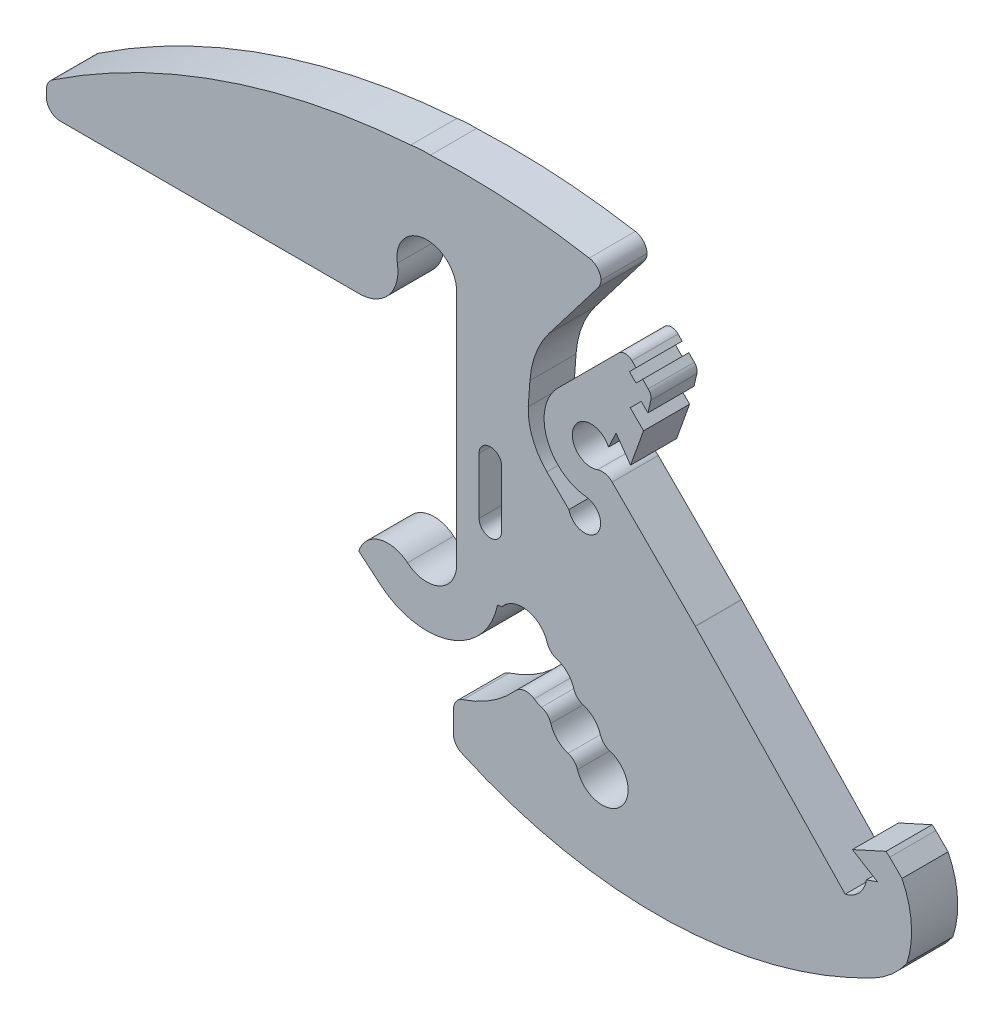
SolidWorks part; units mm, degrees
ref_plane "Front Plane" through (0, 0, 0) normal (0, 0, 1) x (1, 0, 0)
ref_plane "Top Plane" through (0, 0, 0) normal (0, 1, 0) x (1, 0, 0)
ref_plane "Right Plane" through (0, 0, 0) normal (1, 0, 0) x (0, 0, -1)
sketch "Main Geometry" plane through (0, 0, 0) normal (0, 0, 1) x (1, 0, 0)
  line L0 (0, -26.7735) -> (0, 29.7025) construction
  line L1 (-29.8398, 0) -> (33.7757, 0) construction
  line L2 (18, -21.6476) -> (18, 5) construction
  line L3 (18, 5) -> (48.2234, -25.2234) construction
  dimension "vertical offset" = 5
  dimension "horizontal offset" = 18
  dimension "device angle" = 45
sketch "Cart Clip Geometry" plane through (0, 0, 0) normal (0, 0, 1) x (1, 0, 0)
  line L0 (18, 9.2735) -> (18, -10.0482) construction
  line L1 (11.175, 4.575) -> (7.675, -8.575)
  line L2 (7.0852, 12.575) -> (-7.0852, 12.575) construction
  line L3 (-29.8398, 0) -> (33.7757, 0) construction
  line L4 (18, -21.6476) -> (18, 5) construction
  line L6 (-7.0852, 0) -> (7.0852, 0) construction
  line L7 (7.0852, -12.575) -> (-7.0852, -12.575) construction
  line L8 (0, 12.575) -> (-7.5717, 11.2399) construction
  line L9 (0, -12.575) -> (-5.2448, -18.8255) construction
  line L10 (3.175, 12.575) -> (3.175, -12.575)
  line L11 (-11.0052, 10.6345) -> (-10.7668, 9.2824)
  line L12 (-4.9334, -18.4544) -> (-7.2315, -16.526)
  line L13 (11.175, 4.575) -> (11.175, 12.575)
  line L14 (7.675, -12.575) -> (7.675, -8.575)
  arc A0 (-3.1268, 12.0237) -> (3.175, 12.575) centre (0, 12.575) cw
  arc A1 (-2.0409, -15.0072) -> (3.175, -12.575) centre (0, -12.575) ccw
  arc A2 (-11.0052, 10.6345) -> (11.175, 12.575) centre (0, 12.575) cw
  arc A3 (-4.9334, -18.4544) -> (7.675, -12.575) centre (0, -12.575) ccw
  arc A4 (-3.1268, 12.0237) -> (-10.7668, 9.2824) centre (-7.182, 11.3086) cw
  arc A5 (-2.0409, -15.0072) -> (-7.2315, -16.526) centre (-4.1299, -17.4968) ccw
  point P5 (0, 12.575)
  point P10 (0, 0)
  point P36 (18, -0.3874)
  dimension "D1" = 4
  dimension "rail radius" = 3.175
  dimension "bottom rail radius" = 3.175
  dimension "rail separation" = 12.575
  dimension "top clip grab angle" = 10
  dimension "bottom clip grab angle" = 50
  dimension "top clip thickness" = 8
  dimension "bottom clip thickness" = 4.5
  dimension "top clip end extension" = 1.3729
  dimension "bottom clip end extension" = 3
  dimension "top clip vertical extension" = 8
extrude "Cart Clip" add sketch "Cart Clip Geometry" against normal blind 4.9022
sketch "Device Clip Geometry" plane through (0, 0, 0) normal (0, 0, 1) x (1, 0, 0)
  line L0 (30.6822, -8.8343) -> (31.1479, -8.3686) construction
  line L1 (22.2452, 15.0879) -> (21.5381, 14.3808)
  line L2 (44.5165, -21.5165) -> (18, 5)
  line L3 (18, 5) -> (48.2234, -25.2234) construction
  line L4 (18, 5) -> (20.2451, 7.2451)
  line L5 (21.6593, 5.8309) -> (20.2451, 7.2451)
  line L6 (21.6593, 5.8309) -> (23.0381, 9.6846)
  line L7 (23.0381, 9.6846) -> (21.6239, 11.0988)
  line L8 (21.6239, 11.0988) -> (22.7977, 12.2726)
  line L9 (22.7977, 12.2726) -> (23.5048, 11.5655)
  line L10 (23.5048, 11.5655) -> (23.8045, 12.8639)
  line L11 (23.5372, 13.7959) -> (22.9502, 14.3828)
  line L12 (20.3936, 15.5253) -> (13.9341, 9.0659)
  line L13 (13.9341, 1.9948) -> (41.5113, -25.5824)
  line L14 (53.3124, -15.9793) -> (53.8993, -16.5663)
  line L15 (51.082, -16.0117) -> (52.3804, -15.712)
  line L16 (51.7891, -16.7188) -> (51.082, -16.0117)
  line L17 (50.6153, -17.8926) -> (51.7891, -16.7188)
  line L18 (49.2011, -16.4784) -> (50.6153, -17.8926)
  line L19 (45.3474, -17.8572) -> (49.2011, -16.4784)
  line L20 (45.3474, -17.8572) -> (46.7616, -19.2714)
  line L21 (44.5165, -21.5165) -> (46.7616, -19.2714)
  line L22 (55.0418, -19.1229) -> (48.5824, -25.5824)
  line L23 (21.5381, 14.3808) -> (22.2431, 13.6757)
  line L25 (22.2431, 13.6757) -> (22.9502, 14.3828)
  line L26 (22.2452, 15.0879) -> (21.8078, 15.5253)
  line L27 (53.1922, -17.2734) -> (53.8993, -16.5663)
  line L28 (53.8973, -17.9784) -> (53.1922, -17.2734)
  line L29 (54.6044, -17.2713) -> (53.8973, -17.9784)
  line L30 (54.6044, -17.2713) -> (55.0418, -17.7087)
  arc A0 (23.8045, 12.8639) -> (23.5372, 13.7959) centre (22.8301, 13.0888) ccw
  arc A1 (21.8078, 15.5253) -> (20.3936, 15.5253) centre (21.1007, 14.8182) ccw
  arc A2 (53.3124, -15.9793) -> (52.3804, -15.712) centre (52.6053, -16.6864) ccw
  arc A3 (55.0418, -17.7087) -> (55.0418, -19.1229) centre (54.3347, -18.4158) cw
  arc A4 (48.5824, -25.5824) -> (41.5113, -25.5824) centre (45.0468, -22.0468) cw
  arc A5 (13.9341, 9.0659) -> (13.9341, 1.9948) centre (17.4697, 5.5303) ccw
  point P3 (30.915, -8.6015)
  point P17 (31.2583, -8.2583)
  point P28 (27.7227, -11.7938)
  point P30 (23.9291, 13.404)
  point P33 (21.1007, 16.2324)
  point P36 (52.9205, -15.5874)
  point P39 (55.7489, -18.4158)
  point P42 (45.0468, -29.1179)
  point P45 (10.3986, 5.5303)
  dimension "D2" = 1
  dimension "D3" = 1
  dimension "D5" = 5
  dimension "D1" = 4
  dimension "plate thickness" = 3.175
  dimension "board mating width" = 20.5
  dimension "board catch step" = 1
  dimension "plate to board offset" = 3.7
  dimension "board thickness" = 1.66
  dimension "above board offset" = 1.6
  dimension "overall width" = 24.5
  dimension "base thickness" = 5
  dimension "plate width" = 18.75
  dimension "D4" = 16.75
  dimension "board holding step" = 18.5
  dimension "D6" = 1.6186
  dimension "D7" = 0.9971
extrude "Device Clip" add sketch "Device Clip Geometry" against normal blind 4.9022
sketch "Device Clip Flex Relief Geometry" plane through (0, 0, 0) normal (0, 0, 1) x (1, 0, 0)
  line L0 (30.915, -8.6015) -> (31.1479, -8.3686) construction
  circle A0 centre (17.4697, 5.5303) radius 2
  dimension "D1" = 4
sketch "Joint Geometry" plane through (0, 0, 0) normal (0, 0, 1) x (1, 0, 0)
  line L0 (7.675, -8.575) -> (41.5113, -25.5824)
  line L1 (41.5113, -25.5824) -> (13.9341, 1.9948)
  line L2 (13.9341, 1.9948) -> (11.175, 4.575)
  line L3 (11.175, 4.575) -> (7.675, -8.575)
extrude "Joint" add sketch "Joint Geometry" against normal blind 4.9022
fillet "joint fillets" radius 1 4 edges at (7.675, -8.575, -2.4511) (41.5113, -25.5824, -2.4511) (13.9341, 1.9948, -2.4511) (11.175, 4.575, -2.4511)
extrude "Device Clip Flex Relief" cut sketch "Device Clip Flex Relief Geometry" against normal through all
sketch "mark2" plane through (0, 0, 0) normal (0, 0, 1) x (1, 0, 0)
  circle A1 centre (3.175, 3.3755) radius 0.75
sketch "mark3" plane through (0, 0, 0) normal (0, 0, 1) x (1, 0, 0)
  circle A2 centre (3.175, 1.3755) radius 0.75
sketch "mark4" plane through (0, 0, 0) normal (0, 0, 1) x (1, 0, 0)
  circle A3 centre (3.175, -0.6245) radius 0.75
sketch "mark5" plane through (0, 0, 0) normal (0, 0, 1) x (1, 0, 0)
  circle A4 centre (3.175, -2.6245) radius 0.75
sketch "mark6" plane through (0, 0, 0) normal (0, 0, 1) x (1, 0, 0)
  circle A5 centre (3.175, -4.6245) radius 0.75
sketch "mark7" plane through (0, 0, 0) normal (0, 0, 1) x (1, 0, 0)
  circle A6 centre (3.175, -6.6245) radius 0.75
sketch "mark8" plane through (0, 0, 0) normal (0, 0, 1) x (1, 0, 0)
  circle A7 centre (3.175, -8.6245) radius 0.75
extrude "marker1" [suppressed] cut sketch "mark2" against normal blind 25
extrude "marker2" [suppressed] cut sketch "mark3" against normal blind 25
extrude "marker3" [suppressed] cut sketch "mark4" against normal blind 25
extrude "marker4" [suppressed] cut sketch "mark5" against normal blind 25
extrude "marker5" [suppressed] cut sketch "mark6" against normal blind 25
extrude "marker6" [suppressed] cut sketch "mark7" against normal blind 25
extrude "marker7" [suppressed] cut sketch "mark8" against normal blind 25
sketch "Sketch5" plane through (0, 0, 0) normal (0, 0, 1) x (1, 0, 0)
  line L0 (44.4701, -22.2536) -> (28.5503, -5.5503)
  line L1 (44.5165, -21.5165) -> (18.8839, 4.1161) construction
  line L2 (46.7616, -19.2714) -> (28.5503, -5.5503)
  line L3 (46.7616, -19.2714) -> (44.5165, -21.5165) construction
  arc A0 (46.7616, -19.2714) -> (44.4701, -22.2536) centre (43.7623, -19.3383) cw
extrude "SNAP IN RELIEF" cut sketch "Sketch5" against normal blind 6.35
sketch "BOTTOM BEEFUP SKETCH" plane through (0, 0, 0) normal (0, 0, 1) x (1, 0, 0)
  line L0 (10.677, -13.8895) -> (7.5264, -14.0782)
  line L1 (10.675, -9.2825) -> (44.2787, -25.4887)
  line L2 (44.2787, -25.4887) -> (53.8993, -16.5663)
  line L3 (53.8993, -16.5663) -> (55.0418, -17.7087)
  line L4 (50.3984, -26.8103) -> (55.3333, -21.8754)
  line L5 (7.5264, -14.0782) -> (7.2086, -8.7723)
  line L6 (7.2086, -8.7723) -> (10.675, -9.2825)
  line L7 (11.894, -16.9554) -> (10.677, -13.8895)
  line L8 (2.8283, -24.9304) -> (2.8283, -29.2389)
  arc A0 (55.0418, -17.7087) -> (55.3333, -21.8754) centre (52.7908, -19.9597) cw
  arc A1 (11.894, -16.9554) -> (2.8283, -24.9304) centre (0, -12.575) cw
  arc A2 (50.3984, -26.8103) -> (2.8283, -29.2389) centre (24.3794, 15.7331) cw
  arc A3 (-4.9334, -18.4544) -> (7.675, -12.575) centre (0, -12.575) ccw construction
  point P21 (7.5264, -14.0782)
  point P22 (7.2086, -8.7723)
  dimension "D1" = 5
extrude "BOTTOM BEEFUP" add sketch "BOTTOM BEEFUP SKETCH" against normal blind 4.9022
sketch "CABLE HOLE" plane through (0, 0, 0) normal (0, 0, 1) x (1, 0, 0)
  circle A0 centre (10.1626, -15.725) radius 2.75
  dimension "D1" = 5.5
extrude "CABLE HOLE CUT" cut sketch "CABLE HOLE" against normal blind 6.35
sketch "BOX SLIDE BEEF" plane through (0, 0, 0) normal (0, 0, 1) x (1, 0, 0)
  line L0 (-7.182, 7.1908) -> (-40.4406, 7.1908)
  line L1 (-40.4406, 7.1908) -> (-40.4406, 10.131)
  line L2 (-40.4406, 10.131) -> (-4.1553, 22.9487)
  line L3 (-4.1553, 22.9487) -> (-7.182, 7.1908)
  arc A0 (-10.7668, 9.2824) -> (-3.1268, 12.0237) centre (-7.182, 11.3086) ccw construction
  arc A1 (11.175, 12.575) -> (-11.0052, 10.6345) centre (0, 12.575) ccw construction
extrude "SHELF TAIL" add sketch "BOX SLIDE BEEF" against normal blind 4.9022
sketch "BEHIND TOP CLIP BEEF SKETCH" plane through (0, 0, 0) normal (0, 0, 1) x (1, 0, 0)
  line L0 (18.5184, 20.8412) -> (11.175, 11.2548)
  line L1 (18.5184, 20.8412) -> (18.5184, 22.4809)
  line L2 (18.5184, 22.4809) -> (0.5901, 23.7344)
  line L3 (0.5901, 23.7344) -> (11.175, 11.2548)
  line L4 (11.175, 5.009) -> (11.175, 12.575) construction
  arc A0 (11.175, 12.575) -> (-4.1553, 22.9487) centre (0, 12.575) ccw construction
  point P0 (18.5184, 20.8412)
extrude "FRONT TAB BEEF" add sketch "BEHIND TOP CLIP BEEF SKETCH" against normal blind 4.9022
sketch "TOP CURVE" plane through (0, 0, 0) normal (0, 0, 1) x (1, 0, 0)
  line L0 (-40.4406, 10.131) -> (-38.7511, 8.7519)
  line L1 (-38.7511, 8.7519) -> (0, 16.8685)
  line L2 (0, 16.8685) -> (13.1756, 16.8685)
  line L3 (13.1756, 16.8685) -> (18.5184, 22.4809)
  arc A0 (-40.4406, 10.131) -> (18.5184, 22.4809) centre (4.0052, -55.1441) cw
extrude "TOP CURVE EXTRUSION" add sketch "TOP CURVE" against normal blind 4.9022
pattern_linear "LPattern1" count 4 spacing 4 along (0.7071, -0.7071, 0) of "CABLE HOLE CUT"
sketch "Sketch13" plane through (0, 0, 0) normal (0, 0, 1) x (1, 0, 0)
  line L0 (49.2011, -16.4784) -> (48.8113, -16.1381)
  line L1 (45.3474, -17.8572) -> (45.2375, -17.7613)
  line L2 (45.2375, -17.7613) -> (48.8113, -16.1381)
  line L3 (45.3474, -17.8572) -> (49.2011, -16.4784)
extrude "POSCON BOTTOM SNAPBEEF" add sketch "Sketch13" against normal blind 4.9022
sketch "Sketch14" plane through (0, 0, 0) normal (0, 0, 1) x (1, 0, 0)
  line L3 (12.7717, 0.7685) -> (15.1052, -1.5336)
  line L5 (12.471, 5.6443) -> (11.175, 11.2548)
  line L6 (11.175, 11.2548) -> (10.7847, 5.7677)
  arc A0 (13.9337, 1.9953) -> (16.9467, 0.5578) centre (17.4697, 5.5303) ccw
  arc A1 (12.471, 5.6443) -> (13.9337, 1.9953) centre (17.4697, 5.5303) ccw
  arc A2 (16.9467, 0.5578) -> (15.1052, -1.5336) centre (16.7681, -1.1414) cw
  arc A3 (10.7847, 5.7677) -> (12.7717, 0.7685) centre (17.4697, 5.5303) ccw
extrude "POSCON TOP CLIP FLEX RELIEF" cut sketch "Sketch14" against normal blind 6.35
sketch "Sketch15" plane through (0, 0, 0) normal (0, 0, 1) x (1, 0, 0)
  line L0 (6.7591, -1.122) -> (6.7591, -7.122) construction
  line L1 (7.9591, -1.122) -> (7.9591, -7.122)
  line L2 (5.5591, -1.122) -> (5.5591, -7.122)
  arc A0 (7.9591, -1.122) -> (5.5591, -1.122) centre (6.7591, -1.122) ccw
  arc A1 (5.5591, -7.122) -> (7.9591, -7.122) centre (6.7591, -7.122) ccw
  point P2 (6.7591, -4.122)
  dimension "D2" = 1.2
  dimension "D1" = 6
extrude "ZIP TIE SLOT" cut sketch "Sketch15" against normal blind 6.35
sketch "Sketch16" plane through (0, 0, 0) normal (0, 0, 1) x (1, 0, 0)
  line L0 (45.2375, -17.7613) -> (47.9015, -19.3975)
  line L1 (47.9015, -19.3975) -> (45.9622, -20.0708)
  line L2 (45.9622, -20.0708) -> (45.2375, -17.7613)
  line L3 (41.3743, -4.0413) -> (53.0401, -21.5945)
  line L4 (53.0401, -21.5945) -> (50.3984, -26.8103)
  line L5 (50.3984, -26.8103) -> (52.008, -28.2076)
  line L6 (52.008, -28.2076) -> (59.8175, -20.2354)
  line L7 (41.3743, -4.0413) -> (59.8175, -20.2354)
  line L8 (55.0418, -17.7087) -> (53.3124, -15.9793) construction
extrude "POSCON BOTTOM SNAP RELIEF" cut sketch "Sketch16" against normal blind 6.35
fillet "SMALL FILLET" radius 1.5 14 edges at (18.5184, 20.8412, -2.4511) (-40.4406, 7.1908, -2.4511) (12.9115, -15.8045, -2.4511) (15.7399, -18.633, -2.4511) (18.5683, -21.4614, -2.4511) (13.0706, -21.3022, -2.4511) (15.899, -24.1307, -2.4511) (28.5503, -5.5503, -2.4511) (18.8839, 4.1161, -2.4511) (18.5184, 22.4809, -2.4511) (-40.4406, 10.131, -2.4511) (2.8283, -29.2389, -2.4511) (2.8283, -24.9304, -2.4511) (10.488, -19.6924, -2.4511)
sketch "Sketch12" plane through (0, 0, 0) normal (0, 0, 1) x (1, 0, 0)
  line L0 (21.6593, 5.8309) -> (20.1191, 8.0153)
  line L1 (20.1191, 8.0153) -> (19.311, 6.311)
  line L2 (21.6593, 5.8309) -> (19.311, 6.311)
  line L3 (20.2451, 7.2451) -> (21.6593, 5.8309) construction
  arc A1 (19.311, 6.311) -> (18.1413, 3.6465) centre (17.4697, 5.5303) ccw construction
extrude "POSCON TOP SNAP RELIEF" cut sketch "Sketch12" against normal blind 6.35
sketch "poscon cross section slide in" plane through (0, 0, 0) normal (0, 0, 1) x (1, 0, 0)
  line L0 (21.0676, 7.5064) -> (44.3228, -21.9121)
  line L1 (44.3228, -21.9121) -> (46.6763, -20.0516)
  line L2 (46.6763, -20.0516) -> (23.4211, 9.3668)
  line L3 (23.4211, 9.3668) -> (21.0676, 7.5064)
  dimension "D1" = 37.5
  dimension "D2" = 3
fillet "LARGE FILLET" radius 10 3 edges at (50.3984, -26.8103, -2.4511) (53.0401, -21.5945, -2.4511) (11.175, 11.2548, -2.4511)
equation "\"thick\"= .193in"
equation "\"D1@Cart Clip\"=\"thick\""
equation "\"D1@Device Clip\"=\"thick\""
equation "\"D1@Joint\"=\"thick\""
equation "\"D1@BOTTOM BEEFUP\"=\"thick\""
equation "\"D1@SHELF TAIL\"=\"thick\""
equation "\"D1@FRONT TAB BEEF\"=\"thick\""
equation "\"D1@TOP CURVE EXTRUSION\"=\"thick\""
equation "\"D1@POSCON BOTTOM SNAPBEEF\"=\"thick\""
